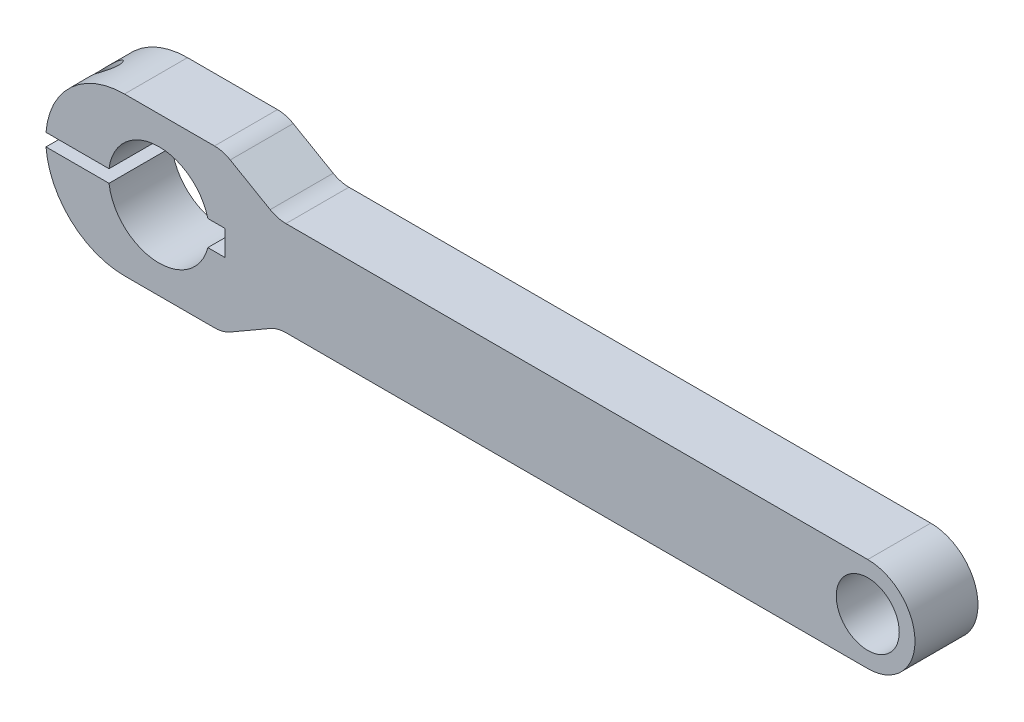
SolidWorks part; units mm, degrees
ref_plane "Plan de face" through (0, 0, 0) normal (0, 0, 1) x (1, 0, 0)
ref_plane "Plan de dessus" through (0, 0, 0) normal (0, 1, 0) x (1, 0, 0)
ref_plane "Plan de droite" through (0, 0, 0) normal (1, 0, 0) x (0, 0, -1)
sketch "Esquisse1" plane through (0, 0, 0) normal (0, 0, 1) x (1, 0, 0)
  line L0 (-75, 177.4931) -> (-300, 177.4931) construction
  line L1 (-262.3913, 162.4931) -> (-75, 162.4931)
  line L3 (-300, 202.4931) -> (-279.7118, 202.4931)
  line L4 (-300, 152.4931) -> (-279.7118, 152.4931)
  line L5 (-262.3913, 192.4931) -> (-75, 192.4931)
  line L6 (-279.7118, 152.4931) -> (-262.3913, 162.4931)
  line L7 (-279.7118, 202.4931) -> (-262.3913, 192.4931)
  circle A0 centre (-300, 177.4931) radius 16
  circle A1 centre (-75, 177.4931) radius 10
  arc A2 (-300, 202.4931) -> (-300, 152.4931) centre (-300, 177.4931) ccw
  arc A3 (-75, 162.4931) -> (-75, 192.4931) centre (-75, 177.4931) ccw
  dimension "D1" = 32
  dimension "D3" = 15
  dimension "D4" = 50
  dimension "D7" = 20
  dimension "D2" = 225
  dimension "D5" = 30
  dimension "D6" = 30
extrude "Boss.-Extru.1" add sketch "Esquisse1" along normal blind 20
fillet "Congé1" radius 10 4 edges at (-262.3913, 162.4931, 10) (-279.7118, 152.4931, 10) (-279.7118, 202.4931, 10) (-262.3913, 192.4931, 10)
sketch "Esquisse2" plane through (0, 0, 20) normal (0, 0, 1) x (1, 0, 0)
  line L1 (-279, 181.4931) -> (-308.8713, 181.4931)
  line L2 (-279, 181.4931) -> (-279, 173.4931)
  line L3 (-279, 173.4931) -> (-308.8713, 173.4931)
  line L4 (-308.8713, 181.4931) -> (-308.8713, 173.4931)
  circle A0 centre (-300, 177.4931) radius 16 construction
  dimension "D1" = 4
  dimension "D2" = 8
  dimension "D3" = 21
extrude "Enlèv. mat.-Extru.1" cut sketch "Esquisse2" against normal through all
sketch "Esquisse3" plane through (0, 0, 0) normal (0, 0, -1) x (-1, 0, 0)
  line L0 (310.961, 202.4931) -> (294.8795, 202.4931)
  line L2 (282.3913, 202.4931) -> (300, 202.4931) construction
  line L4 (310.961, 152.4931) -> (296.0103, 152.4931)
  line L5 (300, 152.4931) -> (282.3913, 152.4931) construction
  line L6 (294.8795, 202.4931) -> (293.7381, 195.6141)
  line L7 (296.0103, 152.4931) -> (293.7381, 159.372)
  arc A0 (310.961, 152.4931) -> (310.961, 202.4931) centre (310.961, 177.4931) ccw
  arc A1 (293.7381, 159.372) -> (293.7381, 195.6141) centre (300, 177.4931) ccw
  dimension "D1" = 50
extrude "Boss.-Extru.2" add sketch "Esquisse3" against normal blind 20
sketch "Esquisse4" plane through (0, 0, 0) normal (0, 0, -1) x (-1, 0, 0)
  line L0 (300, 177.4931) -> (346.4121, 177.4931) construction
  line L1 (314.0952, 179.4931) -> (338.1046, 179.4931)
  line L2 (314.0952, 179.4931) -> (314.0952, 175.4931)
  line L3 (314.0952, 175.4931) -> (338.1046, 175.4931)
  line L4 (338.1046, 179.4931) -> (338.1046, 175.4931)
  dimension "D1" = 2
  dimension "D2" = 2
extrude "Enlèv. mat.-Extru.2" cut sketch "Esquisse4" against normal blind 20
sketch "Esquisse5" plane through (0, 179.4931, 0) normal (0, -1, 0) x (1, 0, 0)
  circle A0 centre (-326.2975, 10) radius 3.5
  dimension "D1" = 7
extrude "Enlèv. mat.-Extru.3" cut sketch "Esquisse5" against normal blind 36
cosmetic thread "Représentation de filetage1" parameters "D2"=8
sketch "Esquisse6" plane through (0, 175.4931, 0) normal (0, 1, 0) x (1, 0, 0)
  circle A0 centre (-326.2975, -10) radius 4.5
  dimension "D1" = 9
extrude "Enlèv. mat.-Extru.4" cut sketch "Esquisse6" against normal blind 36
ref_plane "Plan1" through (0, 170.4931, 0) normal (0, 1, 0) x (-1, 0, 0)
sketch "Esquisse7" plane through (0, 170.4931, 0) normal (0, 1, 0) x (-1, 0, 0)
  circle A0 centre (326.2975, 10) radius 7
  dimension "D1" = 14
extrude "Enlèv. mat.-Extru.5" cut sketch "Esquisse7" against normal blind 36
